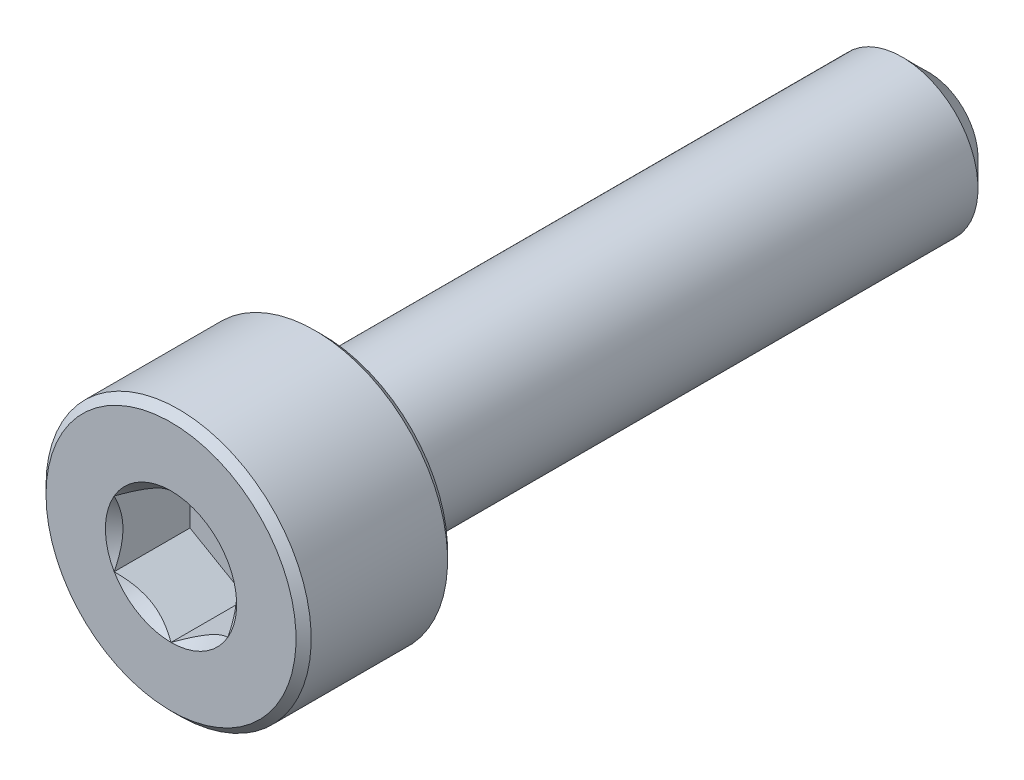
SolidWorks part; units mm, degrees
ref_plane "Front Plane" through (0, 0, 0) normal (0, 0, 1) x (1, 0, 0)
ref_plane "Top Plane" through (0, 0, 0) normal (0, 1, 0) x (1, 0, 0)
ref_plane "Right Plane" through (0, 0, 0) normal (1, 0, 0) x (0, 0, -1)
sketch "Sketch1" plane through (0, 0, 0) normal (1, 0, 0) x (0, 0, -1)
  line L0 (-10, 0) -> (10, 0) construction
  line L1 (10, 0) -> (10, 1.3) construction
  line L2 (10, 1.3) -> (9.3, 2) construction
  line L3 (9.3, 2) -> (-6, 2) construction
  line L5 (-6, 2) -> (-6, 3.5) construction
  line L6 (-6, 3.5) -> (-10, 3.5) construction
  line L7 (-10, 3.5) -> (-10, 0) construction
  line L8 (10, 1.3) -> (10, 2) construction
  line L9 (9.9563, 2.0758) -> (10.3063, 1.4696) construction
  line L10 (10.3063, 1.4696) -> (10.6562, 2.0758) construction
  line L11 (10.6562, 2.0758) -> (9.9563, 2.0758) construction
  line L12 (10.3063, 2.0758) -> (10.3063, 2) construction
  line L13 (10.3063, 1.4696) -> (10.3063, 1.5453) construction
  line L14 (10.2625, 1.5453) -> (10.35, 1.5453) construction
  line L15 (10, 2) -> (10.6125, 2) construction
  line L16 (9.9781, 2.0379) -> (10.6344, 2.0379) construction
  line L17 (10, 0) -> (10, -2) construction
  line L18 (-6.2, 3.5) -> (-6, 3.3) construction
  line L19 (-9.8, 3.5) -> (-10, 3.3) construction
  point P0 (-10, 1.5)
  point P3 (7.55, 2)
  point P4 (0, 0)
  point P22 (10.3063, 1.5453)
  point P24 (-6, 2)
  point P25 (10.3063, 2)
  point P28 (10.3063, 2.0379)
  point P29 (7.55, -2)
  point P31 (-8, 3.5)
  point P37 (-6.7, 3.5)
  point P38 (-9.7, 3.5)
  point P41 (-8, 0)
  dimension "head height" = 4
  dimension "D1" = 45
  dimension "Head Diameter" = 7
  dimension "Thread Size" = 4
  dimension "drive size" = 3
  dimension "Thread Pitch" = 0.7
  dimension "D2" = 0.0875
  dimension "D3" = 0.7
  dimension "D4" = 2.45
  dimension "D7" = 0.2
  dimension "D8" = 0.2
  dimension "D9" = 0.2
  dimension "D10" = 0.1
  dimension "D11" = 0.5
  dimension "length" = 16
  dimension "Drive Depth" = 2
sketch "Sketch2" plane through (0, 0, 0) normal (1, 0, 0) x (0, 0, -1)
  line L1 (-9.8, 3.5) -> (-6.2, 3.5)
  line L4 (9.3, 2) -> (10, 1.3)
  line L5 (10, 1.3) -> (10, 0)
  line L6 (-6.2, 3.5) -> (-6, 3.3) construction
  line L7 (10, 0) -> (-10, 0)
  line L8 (-9.8, 3.5) -> (-10, 3.3) construction
  line L9 (-6.2, 3.5) -> (-6, 3.3)
  line L10 (-9.8, 3.5) -> (-10, 3.3)
  line L11 (-10, 3.3) -> (-10, 0)
  line L12 (-6, 3.3) -> (-6, 2)
  line L13 (-6, 2) -> (9.3, 2)
revolve "Revolve1" add sketch "Sketch2" angle 360 about L7
sketch "Sketch3" plane through (0, 0, 10) normal (0, 0, 1) x (1, 0, 0)
  line L1 (0, 1.7321) -> (-1.5, 0.866)
  line L2 (-1.5, 0.866) -> (-1.5, -0.866)
  line L3 (-1.5, -0.866) -> (0, -1.7321)
  line L4 (0, -1.7321) -> (1.5, -0.866)
  line L5 (1.5, -0.866) -> (1.5, 0.866)
  line L6 (1.5, 0.866) -> (0, 1.7321)
  circle A0 centre (0, 0) radius 1.5 construction
  dimension "D1" = 3
extrude "Cut-Extrude1" cut sketch "Sketch3" against normal up to vertex (2 mm away) up to point (0, 0, 8)
sketch "Sketch4" plane through (0, 0, 10) normal (0, 0, 1) x (1, 0, 0)
  circle A0 centre (0, 0) radius 1.7321
extrude "Cut-Extrude2" cut sketch "Sketch4" against normal blind 0.5 draft 45
ref_plane "Plane1" [suppressed] through (0, 0, 6) normal (0, 0, 1) x (1, 0, 0)
split "Split1" [suppressed] bodies to split 106
sketch "Sketch6" [suppressed] plane through (0, 0, -10) normal (0, 0, -1) x (-1, 0, 0)
  circle A0 centre (0, 0) radius 2
curve "Helix/Spiral1" [suppressed] pitch 0.7 height 16.7 turns 23.8571
sketch "Sketch7" [suppressed] plane through (0, 0, 0) normal (1, 0, 0) x (0, 0, -1)
  line L0 (9.9781, 2.0379) -> (10.6344, 2.0379)
  line L1 (10.6344, 2.0379) -> (10.35, 1.5453)
  line L2 (10.35, 1.5453) -> (10.2625, 1.5453)
  line L3 (10.2625, 1.5453) -> (9.9781, 2.0379)
sweep "Cut-Sweep1" [suppressed] cut profiles "Sketch7" path "Helix/Spiral1"
sketch "Sketch8" [suppressed] plane through (0, 0, 6) normal (0, 0, -1) x (-1, 0, 0)
  circle A0 centre (0, 0) radius 2
extrude "Boss-Extrude1" [suppressed] add sketch "Sketch8" along normal through all draft 45
ref_plane "Plane2" [suppressed] through (0, 0, 8) normal (0, 0, 1) x (1, 0, 0)
sketch "Sketch9" [suppressed] plane through (0, 0, 8) normal (0, 0, 1) x (1, 0, 0)
  line L0 (0, 3.4038) -> (0.0916, 3.4988)
  line L1 (0, 3.4038) -> (-0.0916, 3.4988)
  line L2 (0, 3.5) -> (0, 0) construction
  line L3 (-0.0916, 3.4988) -> (0, 0) construction
  line L4 (0, 0) -> (0.0916, 3.4988) construction
  arc A0 (0.0916, 3.4988) -> (-0.0916, 3.4988) centre (0, 0) ccw
  circle A1 centre (0, 0) radius 3.4038 construction
  dimension "D1" = 7
  dimension "D2" = 6.8075
  dimension "D3" = 3
extrude "Cut-Extrude4" [suppressed] cut sketch "Sketch9" against normal up to vertex and the other way up to vertex
pattern_circular "CirPattern2" [suppressed] count 96 over 360 about axis through (0, 0, 10) along (0, 0, -1) of bodies 113
equation "\"D2@Sketch1\" = \"Thread Pitch@Sketch1\" / 8"
equation "\"D3@Sketch1\" = \"Thread Pitch@Sketch1\""
equation "\"D3@Helix/Spiral1\" = \"length@Sketch1\" + \"Thread Pitch@Sketch1\""
equation "\"D4@Helix/Spiral1\" = \"Thread Pitch@Sketch1\""
equation "\"D4@Sketch1\" = \"Thread Pitch@Sketch1\" * 3.5"
equation "\"D7@Sketch1\"=\"head height@Sketch1\"*.05"
equation "\"D8@Sketch1\"=\"D7@Sketch1\""
equation "\"D9@Sketch1\"=\"D7@Sketch1\""
equation "\"D10@Sketch1\"=\"D7@Sketch1\"/2"
equation "\"D11@Sketch1\"=\"D10@Sketch1\"*5"
equation "\"D1@CirPattern2\"=( 360 / \"D3@Sketch9\" )*0.8"
equation "\"D1@Sketch3\" = \"drive size@Sketch1\""
equation "\"D2@Sketch9\"=\"Head Diameter@Sketch1\" * 0.9725"
